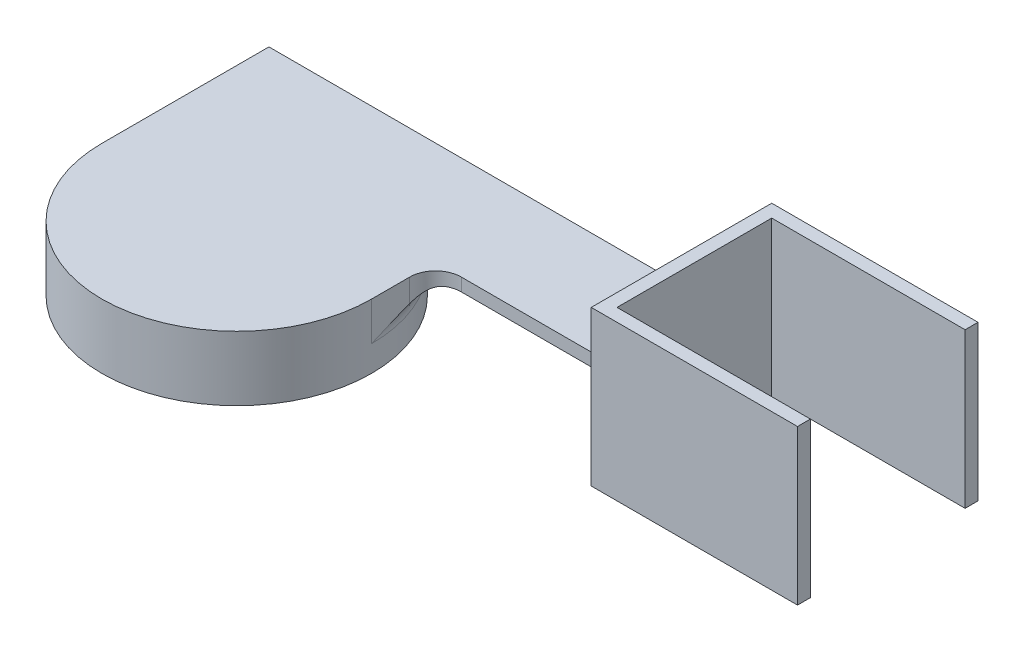
SolidWorks part; units mm, degrees
ref_plane "Front Plane" through (0, 0, 0) normal (0, 0, 1) x (1, 0, 0)
ref_plane "Top Plane" through (0, 0, 0) normal (0, 1, 0) x (1, 0, 0)
ref_plane "Right Plane" through (0, 0, 0) normal (1, 0, 0) x (0, 0, -1)
sketch "Sketch1" plane through (0, 0, 0) normal (0, 1, 0) x (1, 0, 0)
  circle A0 centre (0, 0) radius 33.2105
  dimension "D1" = 66.421
extrude "Boss-Extrude1" add sketch "Sketch1" along normal blind 15.875
sketch "Sketch2" plane through (0, 15.875, 0) normal (0, 1, 0) x (1, 0, 0)
  line L0 (0, 0) -> (-33.2105, 0) construction
  line L1 (0, 0) -> (33.2105, 0) construction
  line L2 (-33.2105, 0) -> (-33.2105, 41.148)
  line L3 (33.2105, 0) -> (33.2105, 15.748)
  line L4 (33.2105, 15.748) -> (81.0895, 15.748)
  line L5 (-33.2105, 41.148) -> (81.0895, 41.148)
  line L6 (81.0895, 15.748) -> (81.0895, 41.148)
  circle A0 centre (0, 0) radius 33.2105 construction
  circle A2 centre (0, 0) radius 33.2105
  arc A3 (-33.2105, 0) -> (33.2105, 0) centre (0, 0) ccw
  dimension "D1" = 114.3
  dimension "D2" = 25.4
  dimension "D3" = 15.748
  dimension "D4" = 0
extrude "Boss-Extrude2" add sketch "Sketch2" against normal blind 3.175
fillet "Fillet1" radius 6.35 1 edges at (33.2105, 14.2875, -15.748)
fillet "Fillet2" radius 6.35 1 edges at (0, 12.7, -33.2105)
sketch "Sketch3" plane through (0, 15.875, 0) normal (0, 1, 0) x (1, 0, 0)
  line L0 (81.0895, 28.448) -> (81.0895, 6.223)
  line L1 (81.0895, 15.748) -> (81.0895, 41.148) construction
  line L2 (81.0895, 6.223) -> (131.8895, 6.223)
  line L3 (131.8895, 6.223) -> (131.8895, 9.398)
  line L4 (131.8895, 9.398) -> (84.2645, 9.398)
  line L5 (84.2645, 9.398) -> (84.2645, 47.498)
  line L6 (84.2645, 47.498) -> (131.8895, 47.498)
  line L7 (131.8895, 47.498) -> (131.8895, 50.673)
  line L8 (131.8895, 50.673) -> (81.0895, 50.673)
  line L9 (81.0895, 28.448) -> (81.0895, 50.673)
  dimension "D1" = 50.8
  dimension "D2" = 38.1
  dimension "D3" = 3.175
  dimension "D4" = 3.175
extrude "Boss-Extrude3" add sketch "Sketch3" against normal mid plane 38.1
